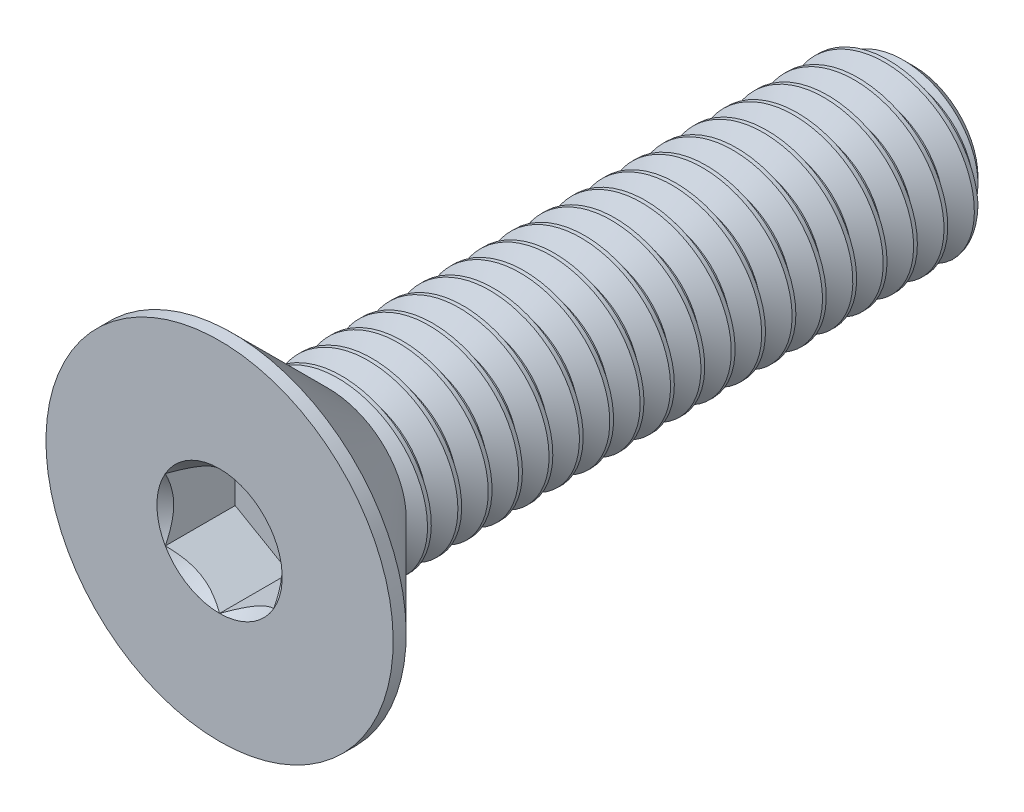
SolidWorks part; units mm, degrees
ref_plane "Front" through (0, 0, 0) normal (0, 0, 1) x (1, 0, 0)
ref_plane "Top" through (0, 0, 0) normal (0, 1, 0) x (1, 0, 0)
ref_plane "Right" through (0, 0, 0) normal (1, 0, 0) x (0, 0, -1)
sketch "Sketch1" plane through (0, 0, 0) normal (1, 0, 0) x (0, 0, -1)
  line L0 (0, 4) -> (0.3, 4) construction
  line L1 (0.3, 4) -> (2.3, 2) construction
  line L2 (0, 2) -> (16, 2)
  line L3 (16, 2) -> (16, 0)
  line L4 (16, 0) -> (0, 0)
  line L5 (0, 0) -> (0, 4) construction
  line L6 (0, 4) -> (0, -4) construction
  line L7 (16, 2) -> (16, -2) construction
  line L8 (0, -4) -> (0.3, -4) construction
  line L9 (0.3, -4) -> (2.3, -2) construction
  line L11 (0, 2) -> (0, 0)
  line L12 (2.3, 2) -> (2.3, 0) construction
  dimension "Head Ht" = 2.3
  dimension "Head Dia" = 8
  dimension "Dia" = 4
  dimension "Lg" = 16
  dimension "Head Angle" = 90
revolve "Revolve1" add sketch "Sketch1" angle 360 mid plane about L4
sketch "Sketch3" plane through (0, 0, -16) normal (0, 0, -1) x (-1, 0, 0)
  circle A0 centre (0, 0) radius 2
curve "Helix/Spiral1" pitch 0.7 height 16 turns 22.8571
sketch "Sketch2" plane through (0, 0, 0) normal (1, 0, 0) x (0, 0, -1)
  line L0 (16, 2) -> (16.6125, 2)
  line L1 (16.6125, 2) -> (16.35, 1.5453)
  line L2 (16.35, 1.5453) -> (16.2625, 1.5453)
  line L3 (16.2625, 1.5453) -> (16, 2)
  line L4 (16.1313, 1.7727) -> (16.4812, 1.7727) construction
  dimension "D1" = 60
  dimension "D2" = 0.0875
  dimension "D3" = 0.35
chamfer "Chamfer1" distance 0.525 angle 45 1 edges at (0, 2, -16)
sweep "Cut-Sweep1" cut profiles "Sketch2" path "Helix/Spiral1"
sketch "Sketch7" plane through (0, 0, 0) normal (1, 0, 0) x (0, 0, -1)
  line L0 (0, 4) -> (0.3, 4) construction
  line L1 (0.3, 4) -> (2.3, 2) construction
  line L2 (0, 4) -> (0.3, 4)
  line L3 (0.3, 4) -> (2.3, 2)
  line L4 (2.3, 2) -> (2.3, 0) construction
  line L5 (2.3, 2) -> (2.3, 0)
  line L7 (0, 0) -> (0, 4) construction
  line L8 (0, 0) -> (0, 4)
  line L9 (0, 0) -> (2.3, 0)
  line L10 (4.4, 0) -> (-4.4, 0) construction
revolve "Revolve2" add sketch "Sketch7" angle 360 mid plane about L9
ref_plane "Plane1" through (0, 0, -2.3) normal (0, 0, 1) x (1, 0, 0)
sketch "Sketch8" plane through (0, 0, -2.3) normal (0, 0, 1) x (1, 0, 0)
  circle A0 centre (0, 0) radius 2
extrude "Boss-Extrude1" add sketch "Sketch8" against normal through all draft 45
sketch "Sketch5" plane through (0, 0, 0) normal (0, 0, 1) x (1, 0, 0)
  line L1 (1.25, -0.7217) -> (1.25, 0.7217)
  line L2 (1.25, 0.7217) -> (0, 1.4434)
  line L3 (0, 1.4434) -> (-1.25, 0.7217)
  line L4 (-1.25, 0.7217) -> (-1.25, -0.7217)
  line L5 (-1.25, -0.7217) -> (0, -1.4434)
  line L6 (0, -1.4434) -> (1.25, -0.7217)
  circle A0 centre (0, 0) radius 1.25 construction
  dimension "Hex" = 2.5
extrude "Cut-Extrude2" cut sketch "Sketch5" against normal blind 1.61
sketch "Sketch6" plane through (0, 0, 0) normal (0, 0, 1) x (1, 0, 0)
  circle A0 centre (0, 0) radius 1.4434
extrude "Cut-Extrude3" cut sketch "Sketch6" against normal blind 1.61 draft 45
sketch "Sketch9" [suppressed] plane through (0, 0, -1.5) normal (0, 0, 1) x (1, 0, 0)
  circle A1 centre (0, 0) radius 1.25
  circle A2 centre (0, 0) radius 1.25
  point P0 (0, 1.25)
  dimension "D1" = 0
extrude "Boss-Extrude2" [suppressed] add sketch "Sketch9" against normal offset from surface (3.5 mm away) 26
fillet "Fillet1" [suppressed] radius 0.4
sketch "Sketch10" plane through (0, 0, 0) normal (1, 0, 0) x (0, 0, -1)
  line L0 (16, 2) -> (16, -2) construction
  point P0 (14.95, -2)
  dimension "D1" = 1.05
equation "\"D3@Helix/Spiral1\" = \"Lg@Sketch1\""
equation "\"D2@Sketch2\" = \"D4@Helix/Spiral1\" * .125"
equation "\"D3@Sketch2\" = \"D4@Helix/Spiral1\" * .5"
equation "\"D1@Chamfer1\" = \"D4@Helix/Spiral1\" * .75"
equation "\"D1@Cut-Extrude2\" = \"Head Ht@Sketch1\" * .7"
equation "\"D1@Sketch10\" = \"D4@Helix/Spiral1\" * 1.5"
equation "\"D1@Cut-Extrude3\" = \"D1@Cut-Extrude2\""
equation "\"D1@Fillet1\" = \"Dia@Sketch1\" * .1"
